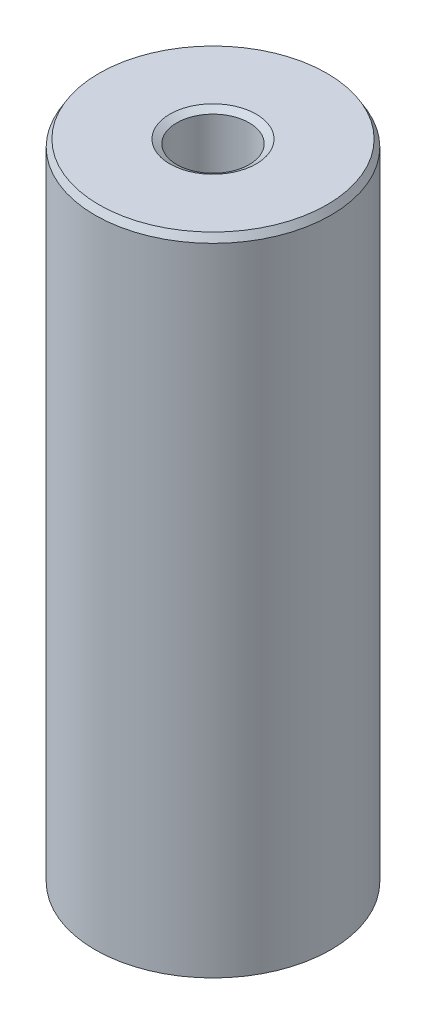
SolidWorks part; units mm, degrees
ref_plane "Front Plane" through (0, 0, 0) normal (0, 0, 1) x (1, 0, 0)
ref_plane "Top Plane" through (0, 0, 0) normal (0, 1, 0) x (1, 0, 0)
ref_plane "Right Plane" through (0, 0, 0) normal (1, 0, 0) x (0, 0, -1)
sketch "Sketch1" plane through (0, 0, 0) normal (0, 1, 0) x (1, 0, 0)
  circle A0 centre (0, 0) radius 5
  dimension "SLEEVE_OD" = 10
extrude "Boss-Extrude1" add sketch "Sketch1" along normal blind 27.4316
sketch "Sketch2" plane through (0, 0, 0) normal (0, 1, 0) x (1, 0, 0)
  circle A0 centre (0, 0) radius 1.5354
  dimension "BORE_D" = 3.0708
extrude "Cut-Extrude1" cut sketch "Sketch2" along normal through all
chamfer "Chamfer1" distance 0.2948 angle 30 4 edges at (0, 27.4316, 1.5354) (0, 0, 1.5354) (0, 0, 5) (0, 27.4316, 5) first distance on face at (0, 27.4316, 1.5354) first distance on face at (0, 0, 1.5354) first distance on face at (0, 27.4316, 5)
